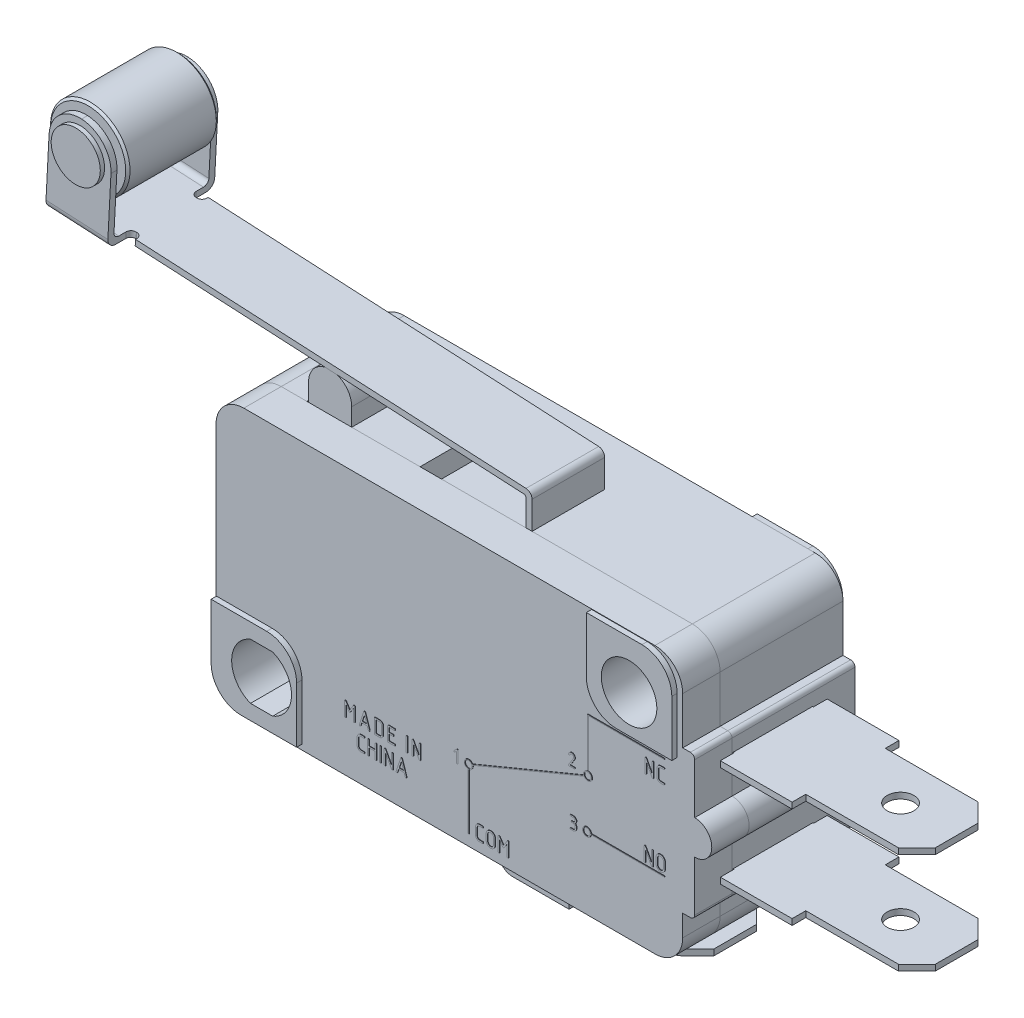
SolidWorks part; units mm, degrees
ref_plane "Front Plane" through (0, 0, 0) normal (0, 0, 1) x (1, 0, 0)
ref_plane "Top Plane" through (0, 0, 0) normal (0, 1, 0) x (1, 0, 0)
ref_plane "Right Plane" through (0, 0, 0) normal (1, 0, 0) x (0, 0, -1)
sketch "Sketch1" plane through (0, 0, 0) normal (0, 0, 1) x (1, 0, 0)
  line L1 (-13.8684, 7.9375) -> (13.8684, 7.9375)
  line L2 (-13.8684, 7.9375) -> (-13.8684, -7.9375)
  line L3 (-13.8684, -7.9375) -> (13.8684, -7.9375)
  line L4 (13.8684, 7.9375) -> (13.8684, -7.9375)
  line L5 (-13.8684, 7.9375) -> (13.8684, -7.9375) construction
  line L6 (-13.8684, -7.9375) -> (13.8684, 7.9375) construction
  point P0 (0, 0)
  dimension "D1" = 15.875
  dimension "D2" = 27.7368
extrude "Boss-Extrude1" add sketch "Sketch1" along normal blind 7.62
sketch "Sketch2" plane through (0, 0, 7.62) normal (0, 0, 1) x (1, 0, 0)
  line L0 (13.8684, 3.4925) -> (14.5796, 3.4925)
  line L1 (13.8684, -7.9375) -> (13.8684, 7.9375) construction
  line L2 (14.5796, 3.4925) -> (14.5796, 0.254)
  line L3 (14.5796, -1.778) -> (14.5796, -5.0165)
  line L4 (14.5796, -5.0165) -> (13.8684, -5.0165)
  line L5 (13.8684, 3.4925) -> (13.8684, -5.0165)
  line L6 (-13.8684, 7.9375) -> (-13.8684, -7.9375) construction
  line L7 (13.8684, -0.762) -> (14.5796, -0.762) construction
  line L8 (13.8684, 7.9375) -> (-13.8684, 7.9375) construction
  arc A0 (14.5796, 0.254) -> (14.5796, -1.778) centre (14.5796, -0.762) cw
  dimension "D1" = 29.464
  dimension "D3" = 1.016
  dimension "D2" = 8.509
  dimension "D4" = 4.445
extrude "Boss-Extrude3" add sketch "Sketch2" against normal through all
sketch "Sketch3" plane through (0, 0, 7.62) normal (0, 0, 1) x (1, 0, 0)
  line L9 (13.8684, -7.9375) -> (13.8684, -5.0165)
  line L10 (13.8684, -5.0165) -> (14.5796, -5.0165)
  line L11 (14.5796, -5.0165) -> (14.5796, -1.778)
  line L12 (14.5796, 0.254) -> (14.5796, 3.4925)
  line L13 (14.5796, 3.4925) -> (13.8684, 3.4925)
  line L14 (13.8684, 3.4925) -> (13.8684, 7.9375)
  line L15 (13.8684, 7.9375) -> (-13.8684, 7.9375)
  line L16 (-13.8684, 7.9375) -> (-13.8684, -7.9375)
  line L17 (-13.8684, -7.9375) -> (13.8684, -7.9375)
  line L18 (13.8684, -7.9375) -> (13.8684, -5.0165)
  line L19 (13.8684, -5.0165) -> (14.5796, -5.0165)
  line L20 (14.5796, -5.0165) -> (14.5796, -1.778)
  line L21 (14.5796, 0.254) -> (14.5796, 3.4925)
  line L22 (14.5796, 3.4925) -> (13.8684, 3.4925)
  line L23 (13.8684, 3.4925) -> (13.8684, 7.9375)
  line L24 (13.8684, 7.9375) -> (-13.8684, 7.9375)
  line L25 (-13.8684, 7.9375) -> (-13.8684, -7.9375)
  line L26 (-13.8684, -7.9375) -> (13.8684, -7.9375)
  arc A1 (14.5796, -1.778) -> (14.5796, 0.254) centre (14.5796, -0.762) ccw
  arc A2 (14.5796, -1.778) -> (14.5796, 0.254) centre (14.5796, -0.762) ccw
  dimension "D1" = 0
extrude "Boss-Extrude4" add sketch "Sketch3" along normal blind 2.54 separate body
ref_plane "Plane3" through (0, 0, 6.985) normal (0, 0, 1) x (1, 0, 0)
fillet "Fillet1" radius 1.651 4 edges at (13.8684, -7.9375, 3.81) (-13.8684, -7.9375, 3.81) (-13.8684, 7.9375, 3.81) (13.8684, 7.9375, 3.81)
fillet "Fillet2" radius 1.651 4 edges at (-13.8684, -7.9375, 8.89) (-13.8684, 7.9375, 8.89) (13.8684, 7.9375, 8.89) (13.8684, -7.9375, 8.89)
sketch "Sketch4" plane through (0, 0, 10.16) normal (0, 0, 1) x (1, 0, 0)
  line L1 (13.8684, 3.4925) -> (13.8684, 6.2865) construction
  line L2 (-12.2174, -7.9375) -> (12.2174, -7.9375) construction
  line L3 (12.2174, 7.9375) -> (-12.2174, 7.9375) construction
  line L4 (-11.5057, -3.4417) -> (-10.1859, -3.4417)
  line L7 (-11.5057, -6.7437) -> (-10.1859, -6.7437)
  circle A0 centre (10.9982, 5.0673) radius 1.651
  arc A4 (-11.5057, -3.4417) -> (-11.5057, -6.7437) centre (-10.8458, -5.0927) ccw
  arc A5 (-10.1859, -6.7437) -> (-10.1859, -3.4417) centre (-10.8458, -5.0927) ccw
  point P7 (-10.8458, -6.7437)
  dimension "D1" = 3.302
  dimension "D2" = 1.2192
  dimension "D3" = 1.2192
  dimension "D4" = 1.1938
  dimension "D5" = 3.556
  dimension "D8" = 21.844
  dimension "D6" = 3.302
  dimension "D9" = 1.651
extrude "Cut-Extrude1" cut sketch "Sketch4" against normal through all
sketch "Sketch6" plane through (0, 0, 10.16) normal (0, 0, 1) x (1, 0, 0)
  line L0 (8.4582, 7.9121) -> (8.4582, 4.6101)
  line L2 (10.2362, 2.8321) -> (13.5382, 2.8321)
  line L3 (13.5382, 2.8321) -> (13.5382, 6.1341)
  line L4 (11.7602, 7.9121) -> (8.4582, 7.9121)
  line L5 (-13.843, -5.8547) -> (-13.843, -2.5527)
  line L7 (-13.843, -2.5527) -> (-10.541, -2.5527)
  line L8 (-8.763, -4.3307) -> (-8.763, -7.6327)
  line L9 (-8.763, -7.6327) -> (-12.065, -7.6327)
  line L12 (-11.5057, -6.7437) -> (-10.1859, -6.7437) construction
  line L13 (-10.1859, -3.4417) -> (-11.5057, -3.4417) construction
  line L14 (-11.5057, -6.7437) -> (-10.1859, -6.7437)
  line L15 (-10.1859, -3.4417) -> (-11.5057, -3.4417)
  line L16 (-13.8684, 6.2865) -> (-13.8684, -6.2865) construction
  line L17 (12.2174, 7.9375) -> (-12.2174, 7.9375) construction
  arc A0 (8.4582, 4.6101) -> (10.2362, 2.8321) centre (10.2362, 4.6101) ccw
  arc A1 (13.5382, 6.1341) -> (11.7602, 7.9121) centre (11.7602, 6.1341) ccw
  circle A2 centre (10.9982, 5.0673) radius 1.651 construction
  arc A3 (-10.541, -2.5527) -> (-8.763, -4.3307) centre (-10.541, -4.3307) cw
  arc A4 (-12.065, -7.6327) -> (-13.843, -5.8547) centre (-12.065, -5.8547) cw
  arc A6 (-11.5057, -3.4417) -> (-11.5057, -6.7437) centre (-10.8458, -5.0927) ccw construction
  arc A7 (-10.1859, -6.7437) -> (-10.1859, -3.4417) centre (-10.8458, -5.0927) ccw construction
  arc A8 (-10.1859, -6.7437) -> (-10.1859, -3.4417) centre (-10.8458, -5.0927) ccw
  arc A9 (-11.5057, -3.4417) -> (-11.5057, -6.7437) centre (-10.8458, -5.0927) ccw
  circle A10 centre (10.9982, 5.0673) radius 1.651
  dimension "D4" = 2.2352
  dimension "D5" = 1.778
  dimension "D9" = 1.778
  dimension "D10" = 1.778
  dimension "D1" = 5.08
  dimension "D2" = 5.08
  dimension "D3" = 2.54
  dimension "D6" = 5.08
  dimension "D7" = 5.08
  dimension "D8" = 2.54
  dimension "D11" = 0.0254
  dimension "D12" = 0.0254
extrude "Cut-Extrude2" cut sketch "Sketch6" against normal blind 0.3175 flip side to cut
sketch "Sketch7" plane through (0, 0, 0) normal (0, 0, -1) x (-1, 0, 0)
  line L2 (10.1859, -6.7437) -> (11.5057, -6.7437)
  line L3 (11.5057, -3.4417) -> (10.1859, -3.4417)
  line L4 (-8.4582, 4.6101) -> (-8.4582, 7.9121)
  line L5 (-13.5382, 2.8321) -> (-10.2362, 2.8321)
  line L6 (-13.5382, 6.1341) -> (-13.5382, 2.8321)
  line L7 (-8.4582, 7.9121) -> (-11.7602, 7.9121)
  line L8 (-8.4582, 4.6101) -> (-8.4582, 7.9121)
  line L9 (-13.5382, 2.8321) -> (-10.2362, 2.8321)
  line L10 (-13.5382, 6.1341) -> (-13.5382, 2.8321)
  line L11 (-8.4582, 7.9121) -> (-11.7602, 7.9121)
  line L12 (10.1859, -6.7437) -> (11.5057, -6.7437)
  line L13 (11.5057, -3.4417) -> (10.1859, -3.4417)
  line L16 (13.843, -2.5527) -> (10.541, -2.5527)
  line L17 (13.843, -5.8547) -> (13.843, -2.5527)
  line L18 (8.763, -7.6327) -> (12.065, -7.6327)
  line L19 (8.763, -4.3307) -> (8.763, -7.6327)
  line L20 (13.843, -2.5527) -> (10.541, -2.5527)
  line L21 (13.843, -5.8547) -> (13.843, -2.5527)
  line L22 (8.763, -7.6327) -> (12.065, -7.6327)
  line L23 (8.763, -4.3307) -> (8.763, -7.6327)
  circle A1 centre (-10.9982, 5.0673) radius 1.651
  arc A2 (-10.2362, 2.8321) -> (-8.4582, 4.6101) centre (-10.2362, 4.6101) ccw
  arc A3 (-11.7602, 7.9121) -> (-13.5382, 6.1341) centre (-11.7602, 6.1341) ccw
  arc A4 (-10.2362, 2.8321) -> (-8.4582, 4.6101) centre (-10.2362, 4.6101) ccw
  arc A5 (-11.7602, 7.9121) -> (-13.5382, 6.1341) centre (-11.7602, 6.1341) ccw
  circle A6 centre (-10.9982, 5.0673) radius 1.651
  arc A8 (10.1859, -3.4417) -> (10.1859, -6.7437) centre (10.8458, -5.0927) ccw
  arc A9 (11.5057, -6.7437) -> (11.5057, -3.4417) centre (10.8458, -5.0927) ccw
  arc A10 (10.1859, -3.4417) -> (10.1859, -6.7437) centre (10.8458, -5.0927) ccw
  arc A11 (11.5057, -6.7437) -> (11.5057, -3.4417) centre (10.8458, -5.0927) ccw
  arc A12 (12.065, -7.6327) -> (13.843, -5.8547) centre (12.065, -5.8547) ccw
  arc A13 (10.541, -2.5527) -> (8.763, -4.3307) centre (10.541, -4.3307) ccw
  arc A14 (12.065, -7.6327) -> (13.843, -5.8547) centre (12.065, -5.8547) ccw
  arc A15 (10.541, -2.5527) -> (8.763, -4.3307) centre (10.541, -4.3307) ccw
  dimension "D1" = 0
  dimension "D2" = 0
  dimension "D3" = 0
  dimension "D4" = 0
extrude "Cut-Extrude3" cut sketch "Sketch7" against normal blind 0.3175 flip side to cut
sketch "Sketch8" plane through (0, 7.9375, 0) normal (0, 1, 0) x (1, 0, 0)
  line L0 (12.2174, -7.62) -> (-12.2174, -7.62) construction
  line L1 (-3.9624, -7.62) -> (-2.6924, -7.62)
  line L2 (-3.9624, -7.62) -> (-3.9624, -3.429)
  line L3 (-3.9624, -3.429) -> (-2.6924, -3.429)
  line L4 (-2.6924, -7.62) -> (-2.6924, -3.429)
  line L5 (-13.8684, -7.62) -> (-13.8684, -0.3175) construction
  dimension "D1" = 9.906
  dimension "D2" = 1.27
  dimension "D3" = 4.191
extrude "Cut-Extrude4" cut sketch "Sketch8" against normal blind 6.35
ref_plane "Plane1" through (0, 2.4765, 0) normal (0, 1, 0) x (1, 0, 0)
sketch "Sketch9" plane through (0, 2.4765, 0) normal (0, 1, 0) x (1, 0, 0)
  line L0 (14.6304, -2.0193) -> (18.8976, -2.0193)
  line L1 (18.8976, -2.0193) -> (18.8976, -2.8321)
  line L2 (18.8976, -2.8321) -> (24.4094, -2.8321)
  line L3 (24.4094, -2.8321) -> (25.5016, -3.9243)
  line L4 (25.5016, -3.9243) -> (25.5016, -6.4643)
  line L5 (25.5016, -6.4643) -> (24.4094, -7.5565)
  line L6 (24.4094, -7.5565) -> (18.8976, -7.5565)
  line L7 (18.8976, -7.5565) -> (18.8976, -8.3693)
  line L8 (18.8976, -8.3693) -> (14.6304, -8.3693)
  line L9 (14.6304, -8.3693) -> (14.6304, -7.5565)
  line L11 (14.5796, -9.8425) -> (13.8684, -9.8425) construction
  line L12 (13.9974, -5.1943) -> (25.5016, -5.1943) construction
  line L13 (14.6304, -2.8321) -> (13.9974, -2.8321)
  line L14 (13.9974, -2.8321) -> (13.9974, -7.5565)
  line L15 (13.9974, -7.5565) -> (14.6304, -7.5565)
  line L16 (14.6304, -2.8321) -> (14.6304, -2.0193)
  line L19 (14.5796, -0.3175) -> (14.5796, -7.62) construction
  line L20 (14.5796, -0.3175) -> (14.5796, -7.62) construction
  circle A0 centre (22.1678, -5.1943) radius 0.7937
  point P12 (14.224, -9.8425)
  point P21 (13.9974, -5.1943)
  dimension "D8" = 1.5875
  dimension "D9" = 2.54
  dimension "D1" = 1.4732
  dimension "D2" = 4.7244
  dimension "D3" = 6.35
  dimension "D4" = 0.0508
  dimension "D5" = 2.54
  dimension "D6" = 10.922
  dimension "D7" = 6.604
extrude "Boss-Extrude5" add sketch "Sketch9" against normal blind 0.3556 separate body
ref_plane "Plane2" through (0, -3.8735, 0) normal (0, 1, 0) x (1, 0, 0)
sketch "Sketch10" plane through (0, -3.8735, 0) normal (0, 1, 0) x (1, 0, 0)
  line L14 (13.9974, -7.5565) -> (14.6304, -7.5565)
  line L15 (13.9974, -2.8321) -> (13.9974, -7.5565)
  line L16 (14.6304, -2.8321) -> (13.9974, -2.8321)
  line L17 (14.6304, -2.0193) -> (14.6304, -2.8321)
  line L18 (18.8976, -2.0193) -> (14.6304, -2.0193)
  line L19 (18.8976, -2.8321) -> (18.8976, -2.0193)
  line L20 (24.4094, -2.8321) -> (18.8976, -2.8321)
  line L21 (25.5016, -3.9243) -> (24.4094, -2.8321)
  line L22 (25.5016, -6.4643) -> (25.5016, -3.9243)
  line L23 (24.4094, -7.5565) -> (25.5016, -6.4643)
  line L24 (18.8976, -7.5565) -> (24.4094, -7.5565)
  line L25 (18.8976, -8.3693) -> (18.8976, -7.5565)
  line L26 (14.6304, -8.3693) -> (18.8976, -8.3693)
  line L27 (14.6304, -7.5565) -> (14.6304, -8.3693)
  line L28 (13.9974, -7.5565) -> (14.6304, -7.5565)
  line L29 (13.9974, -2.8321) -> (13.9974, -7.5565)
  line L30 (14.6304, -2.8321) -> (13.9974, -2.8321)
  line L31 (14.6304, -2.0193) -> (14.6304, -2.8321)
  line L32 (18.8976, -2.0193) -> (14.6304, -2.0193)
  line L33 (18.8976, -2.8321) -> (18.8976, -2.0193)
  line L34 (24.4094, -2.8321) -> (18.8976, -2.8321)
  line L35 (25.5016, -3.9243) -> (24.4094, -2.8321)
  line L36 (25.5016, -6.4643) -> (25.5016, -3.9243)
  line L37 (24.4094, -7.5565) -> (25.5016, -6.4643)
  line L38 (18.8976, -7.5565) -> (24.4094, -7.5565)
  line L39 (18.8976, -8.3693) -> (18.8976, -7.5565)
  line L40 (14.6304, -8.3693) -> (18.8976, -8.3693)
  line L41 (14.6304, -7.5565) -> (14.6304, -8.3693)
  circle A1 centre (22.1678, -5.1943) radius 0.7937
  circle A2 centre (22.1678, -5.1943) radius 0.7937
  dimension "D1" = 0
  dimension "D2" = 0
extrude "Boss-Extrude6" add sketch "Sketch10" along normal blind 0.3556
fillet "Fillet3" radius 0.254 2 edges at (14.5796, 3.4925, 8.7312) (14.5796, -5.0165, 8.7312)
fillet "Fillet4" radius 0.254 2 edges at (14.5796, -5.0165, 3.9687) (14.5796, 3.4925, 3.9687)
ref_plane "Plane4" through (0, 0, 8.0645) normal (0, 0, 1) x (1, 0, 0)
sketch "Sketch11" plane through (0, 0, 8.0645) normal (0, 0, 1) x (1, 0, 0)
  line L0 (1.1176, -7.1546) -> (1.1176, -9.1059)
  line L1 (1.9812, -9.9695) -> (12.0396, -9.9695)
  line L2 (12.0396, -9.9695) -> (12.0396, -9.6139)
  line L3 (12.0396, -9.6139) -> (1.9812, -9.6139)
  line L4 (1.4732, -9.1059) -> (1.4732, -7.1546)
  line L5 (1.4732, -7.1546) -> (1.1176, -7.1546)
  line L6 (-13.8684, 6.2865) -> (-13.8684, -6.2865) construction
  line L7 (-12.2174, -7.9375) -> (12.2174, -7.9375) construction
  arc A1 (1.1176, -9.1059) -> (1.9812, -9.9695) centre (1.9812, -9.1059) ccw
  arc A2 (1.4732, -9.1059) -> (1.9812, -9.6139) centre (1.9812, -9.1059) ccw
  arc A3 (1.4732, -9.1059) -> (1.9812, -9.6139) centre (1.9812, -9.1059) ccw construction
  dimension "D5" = 0.3556
  dimension "D6" = 0.8636
  dimension "D1" = 14.986
  dimension "D2" = 2.032
  dimension "D3" = 0.3556
  dimension "D4" = 0.3556
  dimension "D7" = 10.922
extrude "Boss-Extrude8" add sketch "Sketch11" against normal blind 6.35 separate body
sketch "Sketch12" plane through (0, -9.9695, 0) normal (0, -1, 0) x (1, 0, 0)
  line L0 (5.335, 8.0645) -> (5.335, 7.239)
  line L1 (1.9812, 8.0645) -> (12.0396, 8.0645) construction
  line L2 (5.335, 7.239) -> (10.9474, 7.239)
  line L3 (10.9474, 7.239) -> (12.0396, 6.1595)
  line L4 (12.0396, 1.7145) -> (12.0396, 8.0645) construction
  line L5 (12.0396, 6.1595) -> (12.0396, 8.0645)
  line L6 (12.0396, 8.0645) -> (5.335, 8.0645)
  line L7 (5.335, 1.7145) -> (5.335, 2.54)
  line L8 (1.9812, 1.7145) -> (12.0396, 1.7145) construction
  line L9 (5.335, 2.54) -> (10.9474, 2.54)
  line L10 (10.9474, 2.54) -> (12.0396, 3.6195)
  line L11 (12.0396, 3.6195) -> (12.0396, 1.7145)
  line L12 (12.0396, 1.7145) -> (5.335, 1.7145)
  line L13 (12.0396, 4.8895) -> (3.466, 4.8895) construction
  dimension "D1" = 4.699
  dimension "D2" = 2.54
  dimension "D3" = 1.0922
extrude "Cut-Extrude5" cut sketch "Sketch12" against normal blind 0.3556
sketch "Sketch13" plane through (0, -9.9695, 0) normal (0, -1, 0) x (1, 0, 0)
  line L0 (12.0396, 4.8895) -> (7.2745, 4.8895) construction
  line L1 (12.0396, 3.6195) -> (12.0396, 6.1595) construction
  circle A0 centre (8.7058, 4.8895) radius 0.7937
  dimension "D1" = 1.5875
  dimension "D2" = 2.54
extrude "Cut-Extrude6" cut sketch "Sketch13" against normal blind 0.3556
sketch "Sketch14" plane through (1.1176, 0, 0) normal (-1, 0, 0) x (0, 0, 1)
  line L0 (7.62, -7.9375) -> (0.3175, -7.9375) construction
  line L1 (0.8586, -7.9375) -> (2.54, -7.9375)
  line L2 (0.8586, -7.9375) -> (0.8586, -7.9883)
  line L3 (0.8586, -7.9883) -> (2.54, -7.9883)
  line L4 (2.54, -7.9375) -> (2.54, -7.9883)
  line L5 (9.8425, -7.9375) -> (7.62, -7.9375) construction
  line L6 (9.8824, -7.9375) -> (7.239, -7.9375)
  line L7 (9.8824, -7.9375) -> (9.8824, -7.9883)
  line L8 (9.8824, -7.9883) -> (7.239, -7.9883)
  line L9 (7.239, -7.9375) -> (7.239, -7.9883)
  line L10 (4.8895, -9.9695) -> (4.8895, -6.9989) construction
  line L11 (1.7145, -9.9695) -> (8.0645, -9.9695) construction
  dimension "D1" = 4.699
  dimension "D2" = 0.0508
extrude "Cut-Extrude7" cut sketch "Sketch14" against normal blind 0.3556
sketch "Sketch15" plane through (0, 7.9375, 0) normal (0, 1, 0) x (1, 0, 0)
  line L0 (12.2174, -7.62) -> (-12.2174, -7.62) construction
  line L1 (-10.6934, -7.62) -> (-8.0264, -7.62)
  line L2 (-10.6934, -7.62) -> (-10.6934, -3.556)
  line L3 (-10.6934, -3.556) -> (-8.0264, -3.556)
  line L4 (-8.0264, -7.62) -> (-8.0264, -3.556)
  line L5 (-13.8684, -7.62) -> (-13.8684, -0.3175) construction
  dimension "D1" = 4.064
  dimension "D2" = 2.667
  dimension "D3" = 3.175
extrude "Cut-Extrude8" cut sketch "Sketch15" against normal blind 3.175
sketch "Sketch16" plane through (0, 4.7625, 0) normal (0, 1, 0) x (1, 0, 0)
  line L8 (-10.6426, -3.6068) -> (-10.6426, -7.5692)
  line L9 (-10.6426, -7.5692) -> (-8.0772, -7.5692)
  line L10 (-8.0772, -7.5692) -> (-8.0772, -3.6068)
  line L11 (-8.0772, -3.6068) -> (-10.6426, -3.6068)
  line L12 (-10.6426, -3.6068) -> (-10.6426, -7.5692)
  line L13 (-10.6426, -7.5692) -> (-8.0772, -7.5692)
  line L14 (-8.0772, -7.5692) -> (-8.0772, -3.6068)
  line L15 (-8.0772, -3.6068) -> (-10.6426, -3.6068)
  dimension "D1" = 0.0508
extrude "Boss-Extrude10" add sketch "Sketch16" along normal blind 5.461
fillet "Fillet5" radius 1.2827 2 edges at (-10.6426, 10.2235, 5.588) (-8.0772, 10.2235, 5.588)
ref_plane "Plane5" through (0, 0, 7.62) normal (0, 0, 1) x (1, 0, 0)
sketch "Sketch18" plane through (0, 0, 7.62) normal (0, 0, 1) x (1, 0, 0)
  line L0 (2.6924, 7.9375) -> (2.6924, 9.589)
  line L1 (12.2174, 7.9375) -> (-12.2174, 7.9375) construction
  line L2 (2.3313, 9.9695) -> (-25.1905, 11.4098)
  line L3 (-25.1905, 11.4098) -> (-25.2091, 11.0547)
  line L4 (-25.2091, 11.0547) -> (2.2068, 9.6199)
  line L5 (2.3368, 9.483) -> (2.3368, 7.9375)
  line L6 (12.2174, 7.9375) -> (-2.6924, 7.9375) construction
  line L7 (2.3368, 7.9375) -> (2.6924, 7.9375)
  line L8 (13.8684, 3.4925) -> (13.8684, 6.2865) construction
  arc A0 (-8.0772, 8.9408) -> (-9.3599, 10.2235) centre (-9.3599, 8.9408) ccw construction
  arc A1 (2.6924, 9.589) -> (2.3313, 9.9695) centre (2.3114, 9.589) ccw
  arc A2 (2.2068, 9.6199) -> (2.3368, 9.483) centre (2.1996, 9.483) cw
  dimension "D4" = 0.381
  dimension "D5" = 0.1372
  dimension "D1" = 11.176
  dimension "D2" = 0.3556
  dimension "D3" = 0.3556
  dimension "D6" = 2.032
  dimension "D7" = 27.94
extrude "Boss-Extrude12" add sketch "Sketch18" against normal blind 4.318 separate body
sketch "Sketch22" plane through (-25.7172, 1.3459, 0) normal (-0.9986, 0.0523, 0) x (0, 0, 1)
  line L0 (5.461, 9.7221) -> (5.461, 12.3141) construction
  line L1 (3.302, 9.7221) -> (7.62, 9.7221) construction
  line L2 (2.6416, 15.5641) -> (2.6416, 10.0777)
  line L3 (2.6416, 10.0777) -> (8.2804, 10.0777)
  line L4 (8.2804, 10.0777) -> (8.2804, 15.5641)
  line L5 (8.2804, 15.5641) -> (8.636, 15.5641)
  line L6 (8.636, 15.5641) -> (8.636, 9.7221)
  line L7 (8.636, 9.7221) -> (2.286, 9.7221)
  line L8 (2.286, 9.7221) -> (2.286, 15.5641)
  line L9 (2.286, 15.5641) -> (2.6416, 15.5641)
  line L10 (3.302, 10.0777) -> (7.62, 10.0777) construction
  dimension "D1" = 0.3556
  dimension "D2" = 6.35
  dimension "D3" = 5.842
extrude "Boss-Extrude15" add sketch "Sketch22" against normal blind 3.683
sketch "Sketch23" plane through (0.5267, 10.0639, 0) normal (0.0523, 0.9986, 0) x (0.9986, -0.0523, 0)
  line L0 (-32.4819, -5.461) -> (-19.0229, -5.461) construction
  line L1 (-22.0694, -3.302) -> (-21.4344, -3.302)
  line L2 (-22.0694, -3.302) -> (-22.0694, -3.3782)
  line L3 (-21.7646, -3.683) -> (-21.7392, -3.683)
  line L4 (-21.4344, -3.302) -> (-21.4344, -3.3782)
  line L5 (-22.0694, -7.62) -> (-21.4344, -7.62)
  line L6 (-22.0694, -7.62) -> (-22.0694, -7.5438)
  line L7 (-21.7646, -7.239) -> (-21.7392, -7.239)
  line L8 (-21.4344, -7.62) -> (-21.4344, -7.5438)
  line L10 (-25.7524, -2.6416) -> (-25.7524, -8.2804) construction
  arc A0 (-22.0694, -7.5438) -> (-21.7646, -7.239) centre (-21.7646, -7.5438) cw
  arc A1 (-21.7392, -7.239) -> (-21.4344, -7.5438) centre (-21.7392, -7.5438) cw
  arc A2 (-22.0694, -3.3782) -> (-21.7646, -3.683) centre (-21.7646, -3.3782) ccw
  arc A3 (-21.7392, -3.683) -> (-21.4344, -3.3782) centre (-21.7392, -3.3782) ccw
  point P15 (-25.7524, -5.461)
  dimension "D3" = 0.3048
  dimension "D1" = 3.556
  dimension "D2" = 0.635
extrude "Cut-Extrude9" cut sketch "Sketch23" against normal up to next (0.3556 mm away)
fillet "Fillet6" radius 0.508 2 edges at (-23.3701, 10.9585, 8.636) (-23.3701, 10.9585, 2.286)
fillet "Fillet7" radius 0.3048 2 edges at (-23.3516, 11.3136, 8.2804) (-23.3516, 11.3136, 2.6416)
fillet "Fillet8" radius 1.8415 4 edges at (-24.9038, 16.8887, 2.4638) (-21.2258, 16.6962, 2.4638) (-24.9038, 16.8887, 8.4582) (-21.2258, 16.6962, 8.4582)
ref_plane "Plane6" through (0, 0, 8.1534) normal (0, 0, -1) x (-1, 0, 0)
sketch "Sketch24" plane through (0, 0, 8.1534) normal (0, 0, -1) x (-1, 0, 0)
  circle A0 centre (23.1611, 14.9535) radius 2.3622
  dimension "D1" = 4.7244
extrude "Boss-Extrude16" add sketch "Sketch24" along normal offset from surface (5.3848 mm away) 0.127 separate body up to face at (-23.2037, 14.1394, 2.6416)
chamfer "Chamfer1" distance 0.127 angle 45 2 edges at (-25.5233, 14.9535, 8.1534) (-23.1611, 12.5913, 2.7686)
sketch "Sketch25" plane through (0, 0, 2.6416) normal (0, 0, 1) x (1, 0, 0)
  circle A0 centre (-23.1611, 14.9535) radius 0.381
  dimension "D1" = 0.762
extrude "Boss-Extrude17" add sketch "Sketch25" along normal up to surface (5.6388 mm away) separate body up to face at (-23.2037, 14.1394, 8.2804)
sketch "Sketch26" plane through (0, 0, 8.636) normal (0, 0, 1) x (1, 0, 0)
  circle A0 centre (-23.1611, 14.9535) radius 1.4605
  dimension "D1" = 2.921
extrude "Boss-Extrude18" add sketch "Sketch26" along normal blind 0.254
sketch "Sketch27" plane through (0, 0, 2.286) normal (0, 0, -1) x (-1, 0, 0)
  circle A0 centre (23.1611, 14.9535) radius 1.4605
  dimension "D1" = 2.921
extrude "Boss-Extrude19" add sketch "Sketch27" along normal blind 0.254
sketch "Sketch28" plane through (0, 0, 9.8425) normal (0, 0, 1) x (1, 0, 0)
  line L0 (14.5796, 0.254) -> (14.5796, 3.2385) construction
  line L1 (12.8016, 2.4245) -> (8.2296, 2.4245)
  line L2 (12.8016, 2.4245) -> (12.8016, 2.3737)
  line L3 (12.8016, 2.3737) -> (8.2804, 2.3737)
  line L5 (12.8016, -3.626) -> (8.448, -3.626)
  line L6 (12.8016, -3.626) -> (12.8016, -3.6768)
  line L7 (12.8016, -3.6768) -> (8.448, -3.6768)
  line L9 (1.1663, -3.6927) -> (8.255, -0.7505) construction
  line L11 (8.2296, 2.4245) -> (8.2296, -0.4978)
  line L12 (8.2296, -0.7505) -> (8.2804, -0.7505) construction
  line L13 (8.2804, 2.3737) -> (8.2804, -0.4978)
  line L14 (1.1865, -7.2688) -> (1.1244, -7.2688)
  line L15 (1.1865, -7.2688) -> (1.1865, -3.9459)
  line L16 (1.1917, -3.6927) -> (1.1409, -3.6927) construction
  line L17 (1.1244, -7.2688) -> (1.1244, -3.9432)
  line L27 (1.4095, -3.6193) -> (8.0313, -0.8709)
  line L28 (1.39, -3.5724) -> (8.0118, -0.8239)
  line L30 (1.1566, -3.6692) -> (8.2453, -0.7271) construction
  line L31 (1.1761, -3.7162) -> (8.2647, -0.774) construction
  arc A0 (8.448, -3.626) -> (8.448, -3.6768) centre (8.1953, -3.6514) ccw
  circle A1 centre (8.1953, -3.6514) radius 0.2032
  arc A2 (8.2296, -0.4978) -> (8.0118, -0.8239) centre (8.255, -0.7505) ccw
  circle A3 centre (8.1953, -3.6514) radius 0.254 construction
  circle A4 centre (8.255, -0.7505) radius 0.2032
  arc A5 (1.1865, -3.9459) -> (1.4095, -3.6193) centre (1.1663, -3.6927) ccw
  circle A6 centre (8.255, -0.7505) radius 0.254 construction
  circle A7 centre (1.1663, -3.6927) radius 0.2032
  circle A9 centre (1.1663, -3.6927) radius 0.254 construction
  arc A16 (1.39, -3.5724) -> (1.1244, -3.9432) centre (1.1663, -3.6927) ccw
  arc A17 (8.0313, -0.8709) -> (8.2804, -0.4978) centre (8.255, -0.7505) ccw
  point P18 (8.4382, -3.5771)
  point P23 (8.4979, -0.6763)
  point P36 (1.3927, -3.545)
  dimension "D6" = 0.508
  dimension "D8" = 0.508
  dimension "D11" = 0.508
  dimension "D2" = 4.572
  dimension "D3" = 1.778
  dimension "D4" = 0.0508
  dimension "D5" = 3.175
  dimension "D10" = 0.0508
  dimension "D7" = 0.0508
  dimension "D9" = 0.0508
  dimension "D12" = 0.0508
  dimension "D14" = 0.0254
  dimension "D15" = 0.0254
extrude "Boss-Extrude20" add sketch "Sketch28" along normal blind 0.0254
sketch "Sketch29" plane through (0, 0, 9.8425) normal (0, 0, 1) x (1, 0, 0)
  line L0 (-6.3933, -4.9486) -> (-1.5009, -4.9486) construction
  line L1 (-6.1271, -6.2541) -> (-1.8431, -6.2541) construction
  line L2 (1.4935, -7.355) -> (3.5544, -7.355) construction
  line L3 (11.3163, -3.5177) -> (13.1206, -3.5177) construction
  line L4 (11.3163, 1.045) -> (13.1206, 1.045) construction
  line L5 (0, -4.0162) -> (0.8234, -4.0162) construction
  line L6 (6.8924, -4.0045) -> (7.8746, -4.0045) construction
  line L7 (6.8116, -0.7869) -> (7.7841, -0.7869) construction
  text T0 "MADE IN" font "GOST Common" height 0.889
  text T1 "CHINA" font "GOST Common" height 0.889
  text T2 "COM" font "GOST Common" height 0.889
  text T3 "NO" font "GOST Common" height 0.889
  text T4 "NC" font "GOST Common" height 0.889
  text T6 "1" font "GOST Common" height 0.762
  text T7 "2" font "GOST Common" height 0.762
  text T8 "3" font "GOST Common" height 0.762
extrude "Boss-Extrude22" add sketch "Sketch29" along normal blind 0.0254
